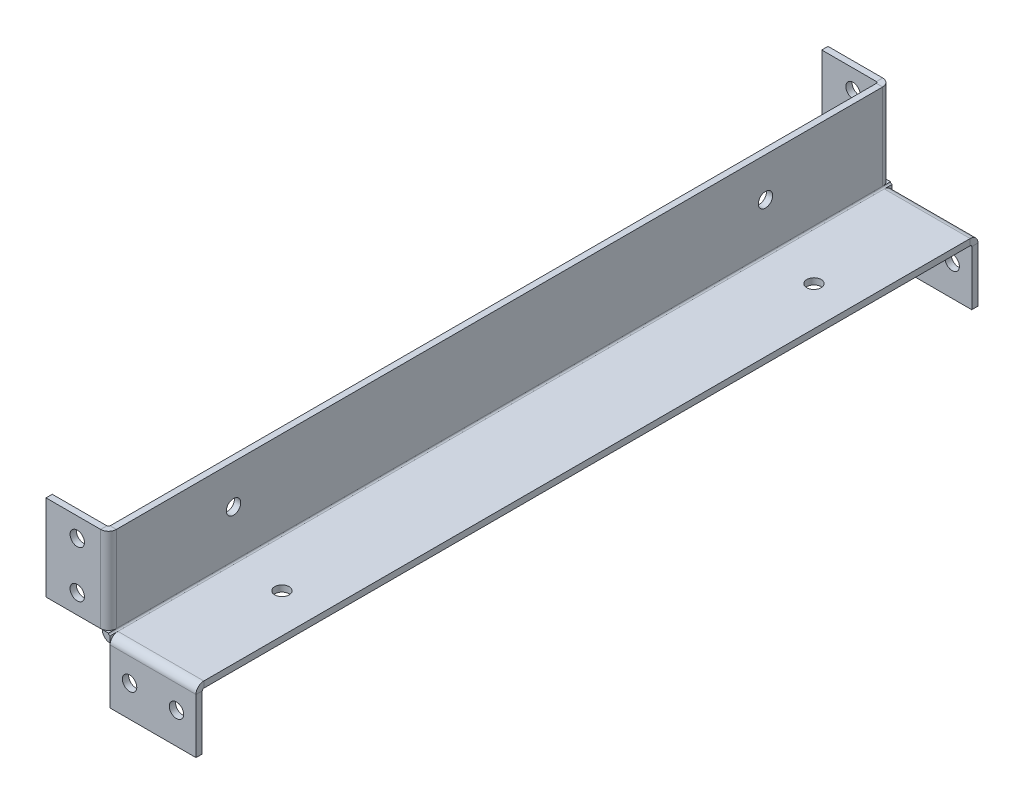
SolidWorks part; units mm, degrees
note: The reader was unsure of these and kept them because the rebuilt part matched: flange length of "Edge-Flange1", "Edge-Flange2".
ref_plane "Front Plane" through (0, 0, 0) normal (0, 0, 1) x (1, 0, 0)
ref_plane "Top Plane" through (0, 0, 0) normal (0, 1, 0) x (1, 0, 0)
ref_plane "Right Plane" through (0, 0, 0) normal (1, 0, 0) x (0, 0, -1)
sketch "Sketch1" plane through (0, 0, 0) normal (0, 1, 0) x (1, 0, 0)
  line L1 (30, 250.25) -> (-30, 250.25)
  line L2 (30, 250.25) -> (30, -250.25)
  line L3 (30, -250.25) -> (-30, -250.25)
  line L4 (-30, 250.25) -> (-30, -250.25)
  line L5 (30, 250.25) -> (-30, -250.25) construction
  line L6 (30, -250.25) -> (-30, 250.25) construction
  point P0 (0, 0)
  dimension "D1" = 60
  dimension "D2" = 500.5
sheet metal parameters "Sheet-Metal1" thickness 4 parameters "D1"=1
base flange "Base-Flange1" sketch "Sketch1" thickness 4 reverse thickness direction yes parameters "D1"=1
edge flange "Edge-Flange1" sketch "Sketch5" flange angle 90 flange length 60 flange position material inside bend radius 1 thickness 4 parameters "D6"=10
sketch "Sketch5" plane through (-30, 4, 0) normal (-1, 0, 0) x (0, 0, 1)
  line L2 (-250.25, 0) -> (-250.25, 56)
  line L3 (-250.25, 56) -> (250.25, 56)
  line L4 (250.25, 56) -> (250.25, 0)
  line L5 (-250.25, 0) -> (250.25, 0) construction
  line L6 (-250.25, 0) -> (250.25, 0)
bend "EdgeBend1" bend radius 1 bend angle 90 parameters "D5"=1
edge flange "Edge-Flange2" sketch "Sketch14" flange profiles "Sketch14", "Sketch15", "Sketch16", "Sketch17" flange angle 90 flange length 40 flange position material inside bend radius 1 thickness 4 relief none parameters "D6"=10, "D8"=0.5
sketch "Sketch14" plane through (-30, 0, 250.25) normal (0, 0, -1) x (0, -1, 0)
  line L1 (-5, 0) -> (-60, 0) construction
  line L2 (-60, 0) -> (-60, 36)
  line L3 (-60, 36) -> (-5, 36)
  line L4 (-5, 36) -> (-5, 0)
  line L5 (-5, 0) -> (-60, 0)
sketch "Sketch15" plane through (0, 0, 250.25) normal (0, 0, -1) x (1, 0, 0)
  line L0 (30, 0) -> (-25, 0) construction
  line L1 (30, 0) -> (-25, 0)
  line L2 (30, 0) -> (30, 36)
  line L3 (30, 36) -> (-25, 36)
  line L4 (-25, 36) -> (-25, 0)
sketch "Sketch16" plane through (-30, 0, -250.25) normal (0, 0, 1) x (0, 1, 0)
  line L0 (60, 0) -> (5, 0) construction
  line L1 (60, 0) -> (5, 0)
  line L2 (60, 0) -> (60, 36)
  line L3 (60, 36) -> (5, 36)
  line L4 (5, 36) -> (5, 0)
sketch "Sketch17" plane through (0, 0, -250.25) normal (0, 0, 1) x (-1, 0, 0)
  line L0 (25, 0) -> (-30, 0) construction
  line L1 (25, 0) -> (-30, 0)
  line L2 (25, 0) -> (25, 36)
  line L3 (25, 36) -> (-30, 36)
  line L4 (-30, 36) -> (-30, 0)
bend "EdgeBend2" bend radius 1 bend angle 90 parameters "D5"=2
bend "EdgeBend3" bend radius 1 bend angle 90 parameters "D5"=3
bend "EdgeBend4" bend radius 1 bend angle 90 parameters "D5"=4
bend "EdgeBend5" bend radius 1 bend angle 90 parameters "D5"=5
sketch "Sketch18" plane through (0, 0, 250.25) normal (0, 0, 1) x (1, 0, 0)
  line L0 (-25, 4) -> (30, 4) construction
  line L1 (-26, 60) -> (-26, 5) construction
  line L2 (-66, 60) -> (-31, 60) construction
  line L3 (30, -1) -> (30, -36) construction
  circle A0 centre (-46, 47.5) radius 4.6
  circle A1 centre (-46, 17.5) radius 4.6
  circle A2 centre (-12.5, -16) radius 4.6
  circle A3 centre (17.5, -16) radius 4.6
  dimension "D7" = 9.2
  dimension "D1" = 30
  dimension "D2" = 30
  dimension "D3" = 20
  dimension "D4" = 20
  dimension "D5" = 12.5
  dimension "D6" = 12.5
extrude "Extrude1" cut sketch "Sketch18" against normal through all normal cut yes
sketch "Sketch19" plane through (-26, 0, 0) normal (1, 0, 0) x (0, 0, -1)
  line L0 (-245.25, 60) -> (245.25, 60) construction
  line L1 (-250.25, 5) -> (-250.25, 60) construction
  line L2 (250.25, 5) -> (250.25, 60) construction
  circle A0 centre (-170.25, 35) radius 4.6
  circle A1 centre (170.25, 35) radius 4.6
  dimension "D4" = 9.2
  dimension "D1" = 25
  dimension "D2" = 80
  dimension "D3" = 80
extrude "Extrude2" cut sketch "Sketch19" against normal blind 4 normal cut yes
sketch "Sketch20" plane through (0, 4, 0) normal (0, 1, 0) x (1, 0, 0)
  line L0 (30, -245.25) -> (30, 245.25) construction
  line L1 (-25, -250.25) -> (30, -250.25) construction
  line L2 (30, 250.25) -> (-25, 250.25) construction
  circle A0 centre (5, 170.25) radius 4.6
  circle A1 centre (5, -170.25) radius 4.6
  dimension "D2" = 9.2
  dimension "D1" = 25
  dimension "D3" = 80
  dimension "D4" = 80
extrude "Extrude3" cut sketch "Sketch20" against normal blind 4 normal cut yes
flat pattern "Flat-Pattern1" [suppressed]
sketch "Bend-Lines1" plane through (0, 4, 0) normal (0, 1, 0) x (-1, 0, 0)
  line L0 (25, -126.4012) -> (-30, -126.4012) construction
  line L1 (82.8023, -126.4012) -> (27.8023, -126.4012) construction
  line L2 (-30, 126.4012) -> (25, 126.4012) construction
  line L3 (27.8023, 126.4012) -> (82.8023, 126.4012) construction
  line L4 (26.4012, -130) -> (26.4012, 130) construction
  line L5 (25, -126.4012) -> (-30, -126.4012) construction
  line L6 (82.8023, -126.4012) -> (27.8023, -126.4012) construction
  line L7 (-30, 126.4012) -> (25, 126.4012) construction
  line L8 (27.8023, 126.4012) -> (82.8023, 126.4012) construction
  line L9 (26.4012, -130) -> (26.4012, 130) construction
bend of the flat pattern "Flatten-<EdgeBend1>1"
bend of the flat pattern "Flatten-<EdgeBend2>1"
bend of the flat pattern "Flatten-<EdgeBend3>1"
bend of the flat pattern "Flatten-<EdgeBend4>1"
bend of the flat pattern "Flatten-<EdgeBend5>1"
